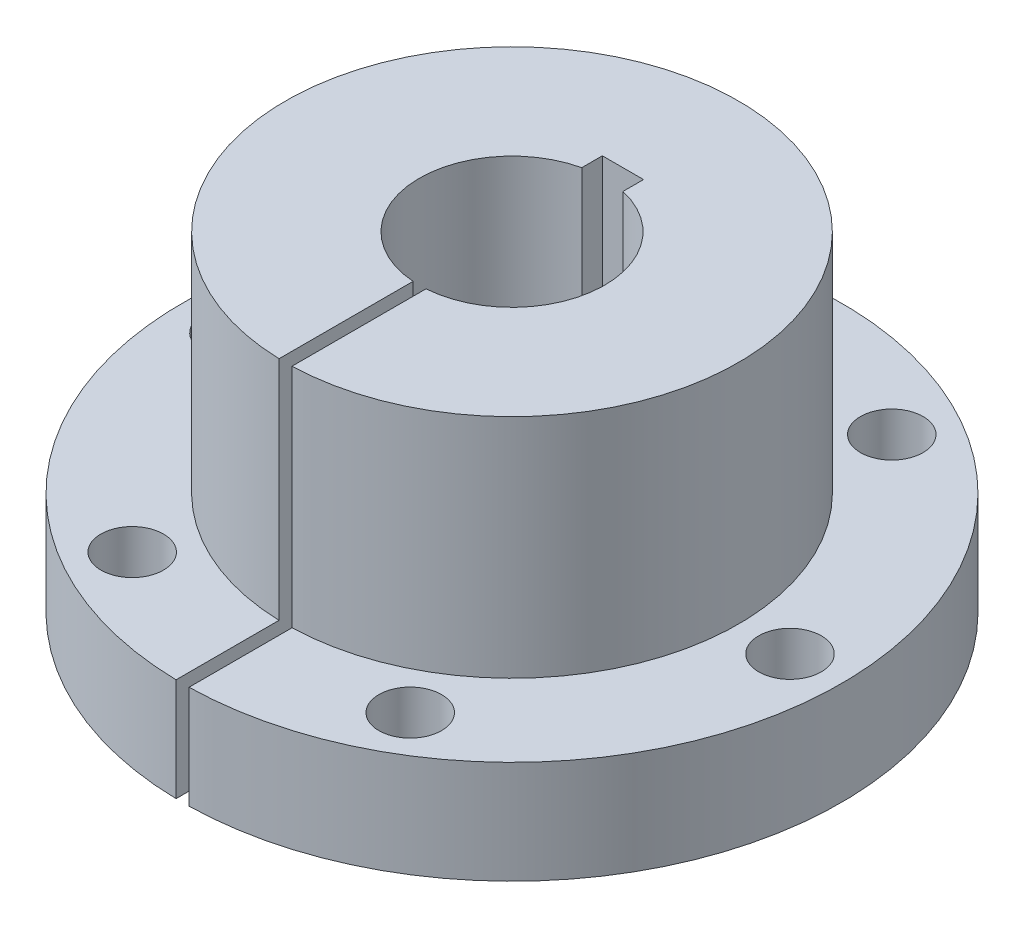
SolidWorks part; units mm, degrees
ref_plane "Front Plane" through (0, 0, 0) normal (0, 0, 1) x (1, 0, 0)
ref_plane "Top Plane" through (0, 0, 0) normal (0, 1, 0) x (1, 0, 0)
ref_plane "Right Plane" through (0, 0, 0) normal (1, 0, 0) x (0, 0, -1)
sketch "Sketch1" plane through (0, 0, 0) normal (0, 1, 0) x (1, 0, 0)
  circle A0 centre (0, 0) radius 25.4
  dimension "D1" = 50.8
extrude "Boss-Extrude1" add sketch "Sketch1" along normal blind 7.9375
sketch "Sketch2" plane through (0, 7.9375, 0) normal (0, 1, 0) x (1, 0, 0)
  circle A0 centre (0, 0) radius 17.4625
  dimension "D1" = 34.925
extrude "Boss-Extrude2" add sketch "Sketch2" along normal blind 17.4625
sketch "Sketch3" plane through (0, 25.4, 0) normal (0, 1, 0) x (1, 0, 0)
  line L0 (-1.5875, 8.5526) -> (1.5875, 8.5526)
  line L1 (-1.5875, 8.5526) -> (-1.5875, 6.9651)
  line L2 (1.5875, 8.5526) -> (1.5875, 6.9651)
  line L6 (-0.5, -7.1262) -> (-0.5, -25.4)
  line L7 (-0.5, -25.4) -> (0.5, -25.4)
  line L8 (0.5, -7.1262) -> (0.5, -25.4)
  arc A0 (-1.5875, 6.9651) -> (-0.5, -7.1262) centre (0, 0) ccw
  circle A1 centre (0, 0) radius 25.4 construction
  arc A2 (0.5, -7.1262) -> (1.5875, 6.9651) centre (0, 0) ccw
  point P10 (0, 0)
  point P12 (0, 0)
  point P13 (0, 0)
  point P16 (0, 0)
  dimension "D1" = 14.2875
  dimension "D2" = 3.175
  dimension "D3" = 1.5875
  dimension "D4" = 1
extrude "Cut-Extrude1" cut sketch "Sketch3" against normal through all
sketch "Sketch4" plane through (0, 7.9375, 0) normal (0, 1, 0) x (1, 0, 0)
  line L0 (-23.8443, 0) -> (-25.4, 0) construction
  line L1 (-19.0182, 0) -> (-17.4625, 0) construction
  line L2 (0, 25.4) -> (-12.5308, 25.4) construction
  circle A0 centre (-21.4312, 0) radius 2.413
  arc A1 (0.5, -25.3951) -> (-0.5, -25.3951) centre (0, 0) ccw construction
  arc A2 (0.5, -17.4553) -> (-0.5, -17.4553) centre (0, 0) ccw construction
  dimension "D1" = 4.826
  dimension "D2" = 25.4
extrude "Cut-Extrude2" cut sketch "Sketch4" against normal through all
pattern_circular "CirPattern1" count 6 over 360 about axis through (0, 7.9375, 0) along (0, 1, 0) of "Cut-Extrude2"
